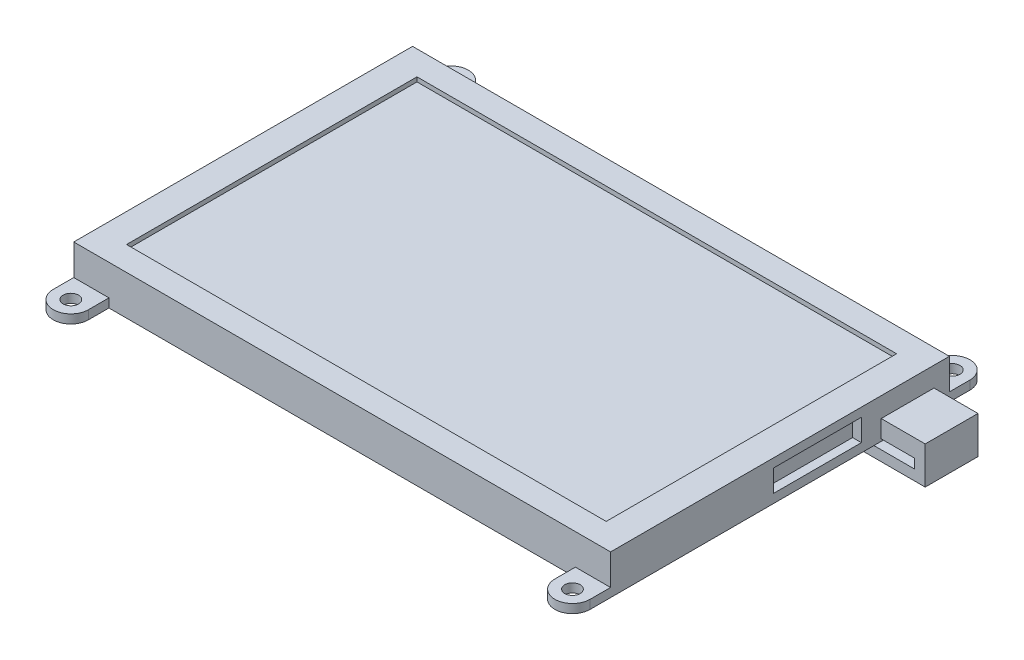
SolidWorks part; units mm, degrees
material "Silicon"
ref_plane "Front Plane" through (0, 0, 0) normal (0, 0, 1) x (1, 0, 0)
ref_plane "Top Plane" through (0, 0, 0) normal (0, 1, 0) x (1, 0, 0)
ref_plane "Right Plane" through (0, 0, 0) normal (1, 0, 0) x (0, 0, -1)
sketch "Sketch1" plane through (0, 0, 0) normal (0, 1, 0) x (1, 0, 0)
  line L1 (0, 0) -> (122, 0)
  line L2 (0, 0) -> (0, 77)
  line L3 (0, 77) -> (122, 77)
  line L4 (122, 0) -> (122, 77)
  dimension "D1" = 77
  dimension "D2" = 122
extrude "Boss-Extrude1" add sketch "Sketch1" along normal blind 9 contours L3 L4 L1 L2
sketch "Sketch2" plane through (0, 9, 0) normal (0, 1, 0) x (1, 0, 0)
  line L0 (61, 77) -> (61, 0) construction
  line L1 (0, 77) -> (122, 77) construction
  line L2 (0, 0) -> (122, 0) construction
  line L3 (0, 38.5) -> (122, 38.5) construction
  line L4 (0, 0) -> (0, 77) construction
  line L5 (122, 0) -> (122, 77) construction
  line L7 (6.5, 71.5) -> (115.5, 71.5)
  line L8 (6.5, 71.5) -> (6.5, 5.5)
  line L9 (6.5, 5.5) -> (115.5, 5.5)
  line L10 (115.5, 71.5) -> (115.5, 5.5)
  line L11 (6.5, 71.5) -> (115.5, 5.5) construction
  line L12 (6.5, 5.5) -> (115.5, 71.5) construction
  point P12 (61, 38.5)
  dimension "D1" = 109
  dimension "D2" = 66
extrude "Cut-Extrude1" cut sketch "Sketch2" against normal blind 1
sketch "Sketch3" plane through (0, 0, 0) normal (0, -1, 0) x (1, 0, 0)
  line L0 (4, -81.66) -> (4, -72.34) construction
  line L1 (0, -81.66) -> (0, -72.34)
  line L2 (8, -81.66) -> (8, -72.34)
  line L3 (0, -77) -> (122, -77) construction
  line L4 (61, -77) -> (61, 9.2683) construction
  line L5 (122, -38.5) -> (0, -38.5) construction
  line L6 (122, 0) -> (122, -77) construction
  line L7 (0, 0) -> (0, -77) construction
  line L8 (118, -81.66) -> (118, -72.34) construction
  line L9 (122, -81.66) -> (122, -72.34)
  line L10 (114, -81.66) -> (114, -72.34)
  line L11 (4, 4.66) -> (4, -4.66) construction
  line L12 (0, 4.66) -> (0, -4.66)
  line L13 (8, 4.66) -> (8, -4.66)
  line L14 (118, 4.66) -> (118, -4.66) construction
  line L15 (122, 4.66) -> (122, -4.66)
  line L16 (114, 4.66) -> (114, -4.66)
  arc A0 (0, -81.66) -> (8, -81.66) centre (4, -81.66) ccw
  arc A1 (8, -72.34) -> (0, -72.34) centre (4, -72.34) ccw
  arc A2 (122, -81.66) -> (114, -81.66) centre (118, -81.66) cw
  arc A3 (114, -72.34) -> (122, -72.34) centre (118, -72.34) cw
  arc A4 (0, 4.66) -> (8, 4.66) centre (4, 4.66) cw
  arc A5 (8, -4.66) -> (0, -4.66) centre (4, -4.66) cw
  arc A6 (122, 4.66) -> (114, 4.66) centre (118, 4.66) ccw
  arc A7 (114, -4.66) -> (122, -4.66) centre (118, -4.66) ccw
  point P2 (4, -77)
  point P7 (0, -77)
  point P8 (4, -85.66)
  point P22 (118, -77)
  point P29 (4, 0)
  point P36 (118, 0)
  dimension "D1" = 8.66
  dimension "D2" = 8
extrude "Boss-Extrude2" add sketch "Sketch3" against normal blind 2
sketch "Sketch4" plane through (0, 0, 0) normal (0, -1, 0) x (1, 0, 0)
  line L0 (61, -77) -> (61, 0) construction
  line L1 (8, -77) -> (114, -77) construction
  line L2 (8, 0) -> (114, 0) construction
  line L3 (122, -38.5) -> (0, -38.5) construction
  line L4 (122, 4.66) -> (122, -81.66) construction
  line L5 (0, 4.66) -> (0, -81.66) construction
  circle A0 centre (4, -81.66) radius 1.75
  circle A1 centre (118, -81.66) radius 1.75
  circle A2 centre (4, 4.66) radius 1.75
  circle A3 centre (118, 4.66) radius 1.75
  dimension "D1" = 3.5
extrude "Cut-Extrude3" cut sketch "Sketch4" against normal blind 4 contours A1 | A3 | A2 | A0
sketch "Sketch5" plane through (122, 0, 0) normal (1, 0, 0) x (0, 0, -1)
  line L0 (77, 9) -> (77, 2) construction
  line L1 (73.5, 4.5) -> (61.5, 4.5)
  line L2 (73.5, 4.5) -> (73.5, 0.5)
  line L3 (73.5, 0.5) -> (61.5, 0.5)
  line L4 (61.5, 4.5) -> (61.5, 0.5)
  line L5 (73.5, 4.5) -> (61.5, 0.5) construction
  line L6 (73.5, 0.5) -> (61.5, 4.5) construction
  line L7 (57, 7) -> (37, 7)
  line L8 (57, 7) -> (57, 2)
  line L9 (57, 2) -> (37, 2)
  line L10 (37, 7) -> (37, 2)
  line L11 (57, 7) -> (37, 2) construction
  line L12 (57, 2) -> (37, 7) construction
  line L13 (-4.66, 0) -> (81.66, 0) construction
  point P0 (67.5, 2.5)
  point P5 (47, 4.5)
  point P14 (73.5, 2.5)
  dimension "D1" = 20
  dimension "D2" = 5
  dimension "D3" = 20
  dimension "D4" = 2
  dimension "D5" = 12
  dimension "D6" = 4
  dimension "D7" = 3.5
  dimension "D8" = 0.5
extrude "Cut-Extrude4" cut sketch "Sketch5" against normal blind 2
sketch "Sketch7" plane through (0, 0, 0) normal (0, -1, 0) x (1, 0, 0)
  line L1 (122, 4.66) -> (122, -81.66) construction
  line L3 (8, -77) -> (114, -77) construction
  circle A2 centre (66, -40) radius 3
  dimension "D1" = 6
  dimension "D2" = 56
  dimension "D3" = 37
extrude "Boss-Extrude3" [suppressed] add sketch "Sketch7" along normal blind 8
sketch "Sketch9" [suppressed] plane through (0, -8, 0) normal (0, -1, 0) x (1, 0, 0)
  line L0 (122, 4.66) -> (122, -81.66) construction
  line L3 (8, -77) -> (114, -77) construction
  circle A1 centre (66.5, -40.5) radius 1.6
  dimension "D1" = 3.2
  dimension "D3" = 36.5
  dimension "D2" = 55.5
extrude "Cut-Extrude5" [suppressed] cut sketch "Sketch9" against normal blind 8
sketch "Sketch11" plane through (122, 0, 0) normal (1, 0, 0) x (0, 0, -1)
  line L1 (73.5, 0.5) -> (61.5, 0.5)
  line L2 (73.5, 0.5) -> (73.5, 4.5)
  line L3 (73.5, 4.5) -> (61.5, 4.5)
  line L4 (61.5, 0.5) -> (61.5, 4.5)
extrude "Boss-Extrude4" add sketch "Sketch11" along normal blind 10 separate body
sketch "Sketch12" plane through (0, 0.5, 0) normal (0, -1, 0) x (1, 0, 0)
  line L0 (132, -61.5) -> (122, -61.5) construction
  line L1 (132, -73.5) -> (129.5841, -73.5)
  line L2 (132, -73.5) -> (132, -61.5)
  line L3 (132, -61.5) -> (129.5841, -61.5)
  line L4 (129.5841, -73.5) -> (129.5841, -61.5)
extrude "Boss-Extrude5" add sketch "Sketch12" along normal blind 4.5
sketch "Sketch13" plane through (129.5841, 0, 0) normal (-1, 0, 0) x (0, 0, 1)
  line L0 (-73.5, -4) -> (-73.5, 0.5) construction
  line L1 (-61.5, -4) -> (-73.5, -4)
  line L2 (-61.5, -4) -> (-61.5, -1.6497)
  line L3 (-61.5, -1.6497) -> (-73.5, -1.6497)
  line L4 (-73.5, -4) -> (-73.5, -1.6497)
extrude "Boss-Extrude6" add sketch "Sketch13" along normal blind 14
extrude "Boss-Extrude7" add sketch "Sketch11<2>" against normal blind 14
sketch "Sketch11<2>" plane through (122, 0, 0) normal (1, 0, 0) x (0, 0, -1) same geometry as "Sketch11"
